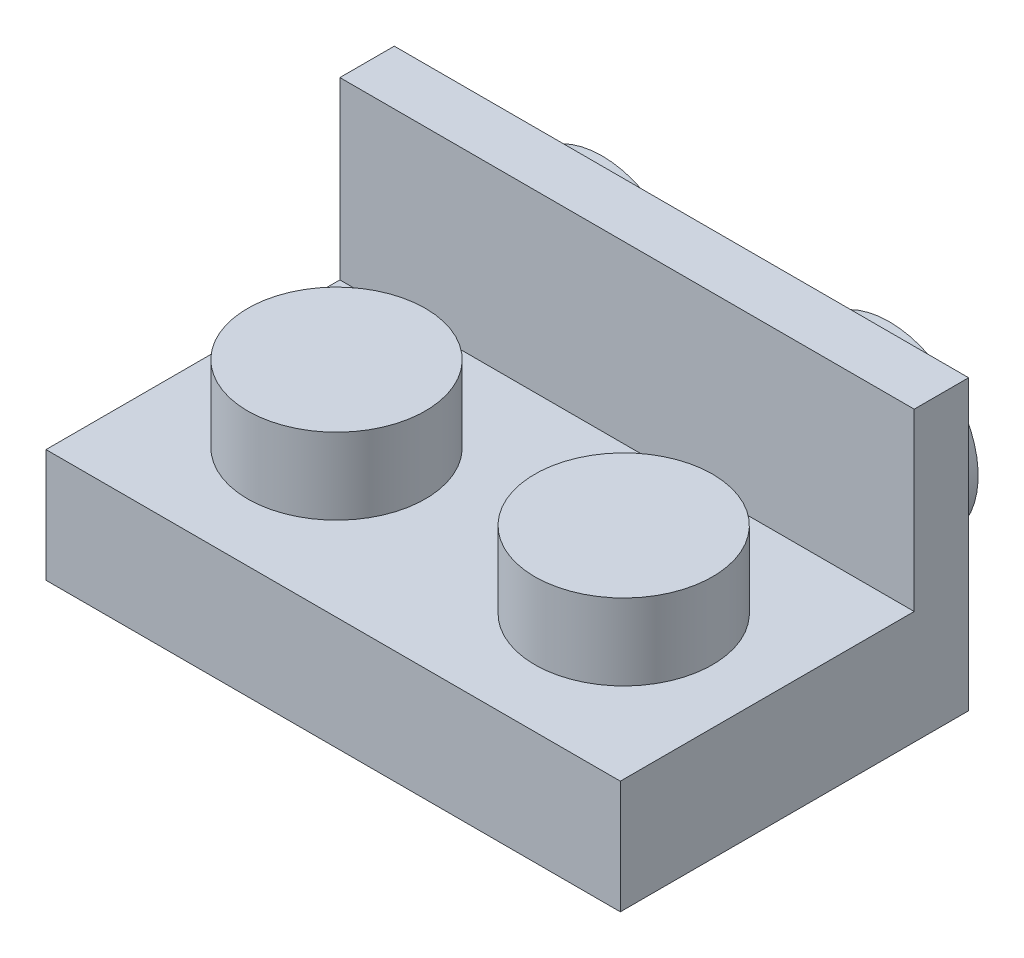
SolidWorks part; units mm, degrees
ref_plane "Front Plane" through (0, 0, 0) normal (0, 0, 1) x (1, 0, 0)
ref_plane "Top Plane" through (0, 0, 0) normal (0, 1, 0) x (1, 0, 0)
ref_plane "Right Plane" through (0, 0, 0) normal (1, 0, 0) x (0, 0, -1)
sketch "Sketch1" plane through (0, 0, 0) normal (1, 0, 0) x (0, 0, -1)
  line L0 (0, 0) -> (0, 4.83)
  line L1 (0, 4.83) -> (1.5, 4.83)
  line L2 (1.5, 4.83) -> (1.5, -3.12)
  line L3 (1.5, -3.12) -> (-8.1, -3.12)
  line L4 (-8.1, -3.12) -> (-8.1, 0)
  line L5 (-8.1, 0) -> (0, 0)
  dimension "D1" = 1.5
  dimension "D2" = 7.95
  dimension "D3" = 4.83
  dimension "D4" = 9.6
extrude "Boss-Extrude1" add sketch "Sketch1" against normal blind 15.83
sketch "Sketch2" plane through (0, 0, 0) normal (0, 1, 0) x (1, 0, 0)
  line L0 (-15.83, 0) -> (-15.83, -8.1) construction
  line L1 (0, 0) -> (0, -8.1) construction
  line L2 (-15.83, -8.1) -> (0, -8.1) construction
  circle A0 centre (-11.8725, -4.05) radius 2.45
  circle A1 centre (-3.9575, -4.05) radius 2.45
  dimension "D1" = 3.9575
  dimension "D2" = 3.9575
  dimension "D5" = 4.9
  dimension "D6" = 4.9
  dimension "D3" = 4.05
  dimension "D4" = 4.05
extrude "Boss-Extrude2" add sketch "Sketch2" along normal blind 2.1
shell "Shell1" thickness 1.5 removed face at (-7.915, -3.12, 3.3)
sketch "Sketch3" plane through (0, 0, -1.5) normal (0, 0, -1) x (-1, 0, 0)
  line L0 (0, -3.12) -> (0, 4.83) construction
  line L2 (15.83, -3.12) -> (15.83, 4.83) construction
  line L3 (15.83, 4.83) -> (0, 4.83) construction
  circle A0 centre (3.9575, 0.855) radius 2.45
  circle A1 centre (3.9575, 0.855) radius 1.47
  circle A2 centre (11.8725, 0.855) radius 2.45
  circle A3 centre (11.8725, 0.855) radius 1.51
  dimension "D5" = 4.9
  dimension "D6" = 4.9
  dimension "D7" = 3.02
  dimension "D8" = 2.94
  dimension "D1" = 3.9575
  dimension "D2" = 3.9575
  dimension "D3" = 3.975
  dimension "D4" = 3.975
extrude "Boss-Extrude3" add sketch "Sketch3" along normal blind 1.77
sketch "Sketch4" plane through (0, -1.5, 0) normal (0, -1, 0) x (1, 0, 0)
  line L0 (-15.83, 8.1) -> (0, 8.1) construction
  line L2 (0, 8.1) -> (0, -1.5) construction
  circle A0 centre (-7.915, 3.3) radius 1.5
  circle A1 centre (-7.915, 3.3) radius 0.66
  dimension "D2" = 7.915
  dimension "D3" = 3
  dimension "D4" = 1.32
  dimension "D1" = 4.8
extrude "Boss-Extrude4" add sketch "Sketch4" along normal offset from surface (1.42 mm away) 0.2 up to face at (-7.915, -3.12, 3.3)
